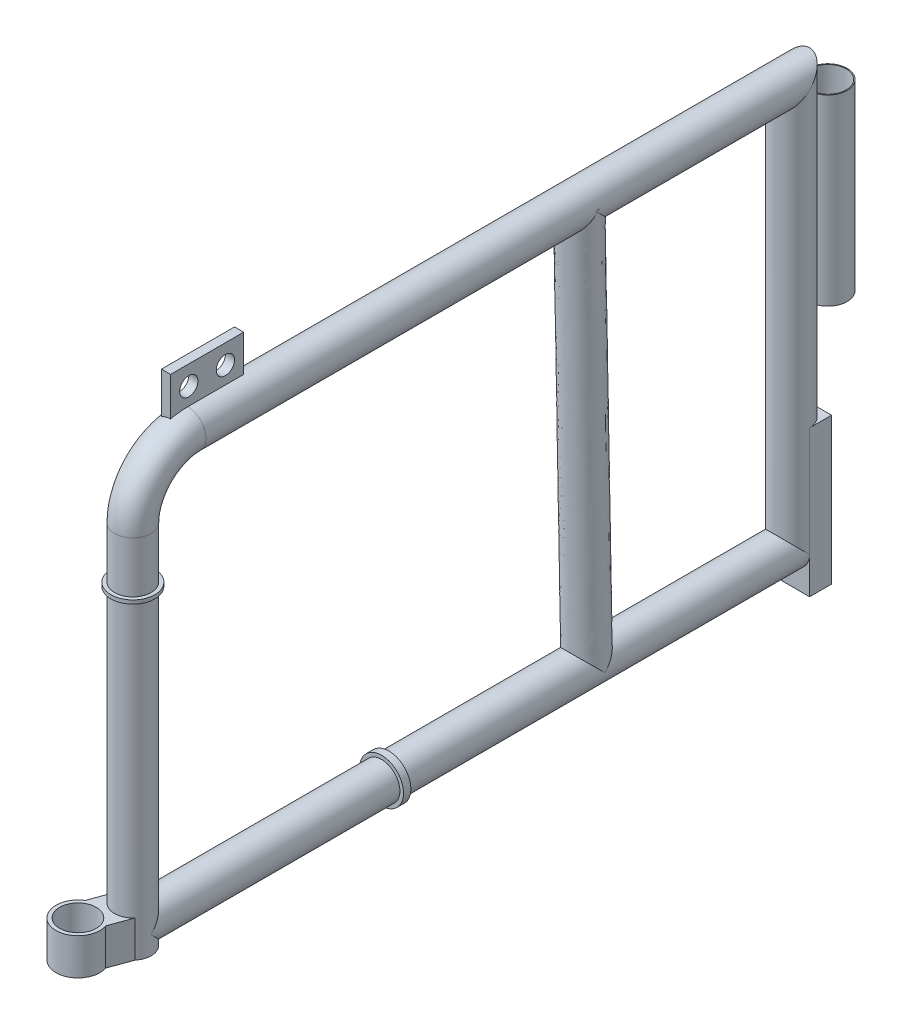
SolidWorks part; units mm, degrees
ref_plane "Front Plane" through (0, 0, 0) normal (0, 0, 1) x (1, 0, 0)
ref_plane "Top Plane" through (0, 0, 0) normal (0, 1, 0) x (1, 0, 0)
ref_plane "Right Plane" through (0, 0, 0) normal (1, 0, 0) x (0, 0, -1)
sketch "Sketch2" plane through (0, 0, 0) normal (0, 0, 1) x (1, 0, 0)
  circle A0 centre (0, 0) radius 12.7
sketch "Sketch3" plane through (0, 0, 0) normal (1, 0, 0) x (0, 0, -1)
  line L0 (0, 0) -> (-457.2, 0)
  line L1 (-457.2, 0) -> (-457.2, 241.3)
  line L2 (-419.1, 279.4) -> (0, 279.4)
  line L3 (0, 279.4) -> (0, 0)
  arc A0 (-419.1, 279.4) -> (-457.2, 241.3) centre (-419.1, 241.3) ccw
  dimension "D1" = 38.1
sweep "Sweep1" add profiles "Sketch2" path "Sketch3"
sketch "Sketch4" plane through (0, 0, 0) normal (1, 0, 0) x (0, 0, -1)
  line L0 (-142.064, 0) -> (-147.3314, 280.7913)
sketch "Sketch5" plane through (0, 0, 0) normal (0, 1, 0) x (1, 0, 0)
  circle A0 centre (0, -142.064) radius 12.7
sweep "Sweep2" add profiles "Sketch5" path "Sketch4"
ref_plane "Plane1" through (0, 0, 304.8) normal (0, 0, 1) x (1, 0, 0)
sketch "Sketch6" plane through (0, 0, 304.8) normal (0, 0, 1) x (1, 0, 0)
  circle A0 centre (0, 0) radius 15.24
ref_plane "Plane2" through (0, 0, 279.4) normal (0, 0, 1) x (1, 0, 0)
sketch "Sketch7" plane through (0, 0, 279.4) normal (0, 0, 1) x (1, 0, 0)
  circle A0 centre (0, 279.4) radius 15.24
sketch "Sketch8" plane through (0, 0, 279.4) normal (0, 0, 1) x (1, 0, 0)
  circle A0 centre (0, 0) radius 15.24
extrude "Boss-Extrude3" add sketch "Sketch8" along normal blind 5.08
sketch "Sketch9" plane through (0, 0, 304.8) normal (0, 0, 1) x (1, 0, 0)
  circle A0 centre (0, 279.4) radius 15.24
extrude "Boss-Extrude4" add sketch "Sketch9" along normal blind 5.08
ref_plane "Plane3" through (0, 139.7, 0) normal (0, 1, 0) x (1, 0, 0)
sketch "Sketch10" plane through (0, 139.7, 0) normal (0, 1, 0) x (1, 0, 0)
  line L0 (0, -304.8) -> (0, 25.4) construction
  line L1 (15.24, -304.8) -> (-15.24, -304.8) construction
  circle A0 centre (0, 25.4) radius 12.7
  circle A1 centre (0, 25.4) radius 13.335
extrude "Boss-Extrude5" add sketch "Sketch10" along normal blind 127
sketch "Sketch11" plane through (0, 0, 309.88) normal (0, 0, 1) x (1, 0, 0)
  circle A0 centre (0, 279.4) radius 12.7 construction
  circle A1 centre (0, 279.4) radius 15.24 construction
  circle A2 centre (0, 279.4) radius 12.7
  circle A3 centre (0, 279.4) radius 15.24
extrude "Cut-Extrude1" cut sketch "Sketch11" against normal blind 78.74
sketch "Sketch12" plane through (0, 0, 0) normal (0, 0, 1) x (1, 0, 0)
  line L0 (0, 0) -> (0, -25.4) construction
  line L1 (0, -25.4) -> (-12.7, -25.4)
  line L2 (0, -25.4) -> (12.7, -25.4)
  line L3 (12.7, -25.4) -> (12.7, 76.2)
  line L4 (12.7, 0) -> (12.7, 279.4) construction
  line L5 (12.7, 76.2) -> (-12.7, 76.2)
  line L6 (-12.7, 279.4) -> (-12.7, 0) construction
  line L7 (-12.7, 76.2) -> (-12.7, -25.4)
extrude "Boss-Extrude6" add sketch "Sketch12" against normal blind 15.24
ref_plane "Plane4" through (0, -12.7, 0) normal (0, 1, 0) x (1, 0, 0)
sketch "Sketch13" plane through (0, -12.7, 0) normal (0, 1, 0) x (1, 0, 0)
  line L0 (-12.7, -457.2) -> (-18.1456, -472.1617)
  line L1 (9.7288, -465.3634) -> (4.2832, -480.3251)
  circle A0 centre (0, -457.2) radius 12.7 construction
  arc A1 (-18.1456, -472.1617) -> (4.2832, -480.3251) centre (-10.1729, -485.1499) ccw
  arc A2 (9.7288, -465.3634) -> (-12.7, -457.2) centre (0, -457.2) ccw
extrude "Boss-Extrude7" add sketch "Sketch13" along normal blind 25.4
sketch "Sketch15" plane through (0, 12.7, 0) normal (0, 1, 0) x (1, 0, 0)
  circle A0 centre (-10.1729, -485.1499) radius 12.7
extrude "Cut-Extrude2" cut sketch "Sketch15" against normal through all
fillet "Fillet1" radius 12.7 rebuild error yes
ref_plane "Plane5" through (0, 279.4, 0) normal (0, 1, 0) x (1, 0, 0)
sketch "Sketch16" plane through (0, 279.4, 0) normal (0, 1, 0) x (1, 0, 0)
  line L0 (0, -469.9) -> (0, -431.038) construction
  line L1 (0, -431.038) -> (-6.35, -431.038)
  line L2 (-6.35, -431.038) -> (-6.35, -380.238)
  line L3 (0, -380.238) -> (0, -431.038)
  line L4 (-6.35, -380.238) -> (0, -380.238)
  arc A0 (-12.7, -457.2) -> (12.7, -457.2) centre (0, -457.2) ccw construction
extrude "Boss-Extrude8" add sketch "Sketch16" along normal blind 38.1
sketch "Sketch17" plane through (0, 0, 0) normal (1, 0, 0) x (0, 0, -1)
  line L2 (-405.638, 304.0887) -> (-431.038, 304.0887) construction
  line L3 (-431.038, 317.5) -> (-431.038, 290.6774) construction
  line L4 (-405.638, 304.0887) -> (-405.638, 317.5) construction
  line L5 (-431.038, 317.5) -> (-380.238, 317.5) construction
  circle A0 centre (-418.338, 304.0887) radius 6.35
  circle A1 centre (-392.938, 304.0887) radius 6.35
extrude "Cut-Extrude3" cut sketch "Sketch17" against normal blind 38.1
ref_plane "Plane6" through (0, 203.2, 0) normal (0, 1, 0) x (1, 0, 0)
sketch "Sketch18" plane through (0, 203.2, 0) normal (0, 1, 0) x (1, 0, 0)
  circle A0 centre (0, -457.2) radius 15.24
extrude "Boss-Extrude9" add sketch "Sketch18" along normal blind 2.54
